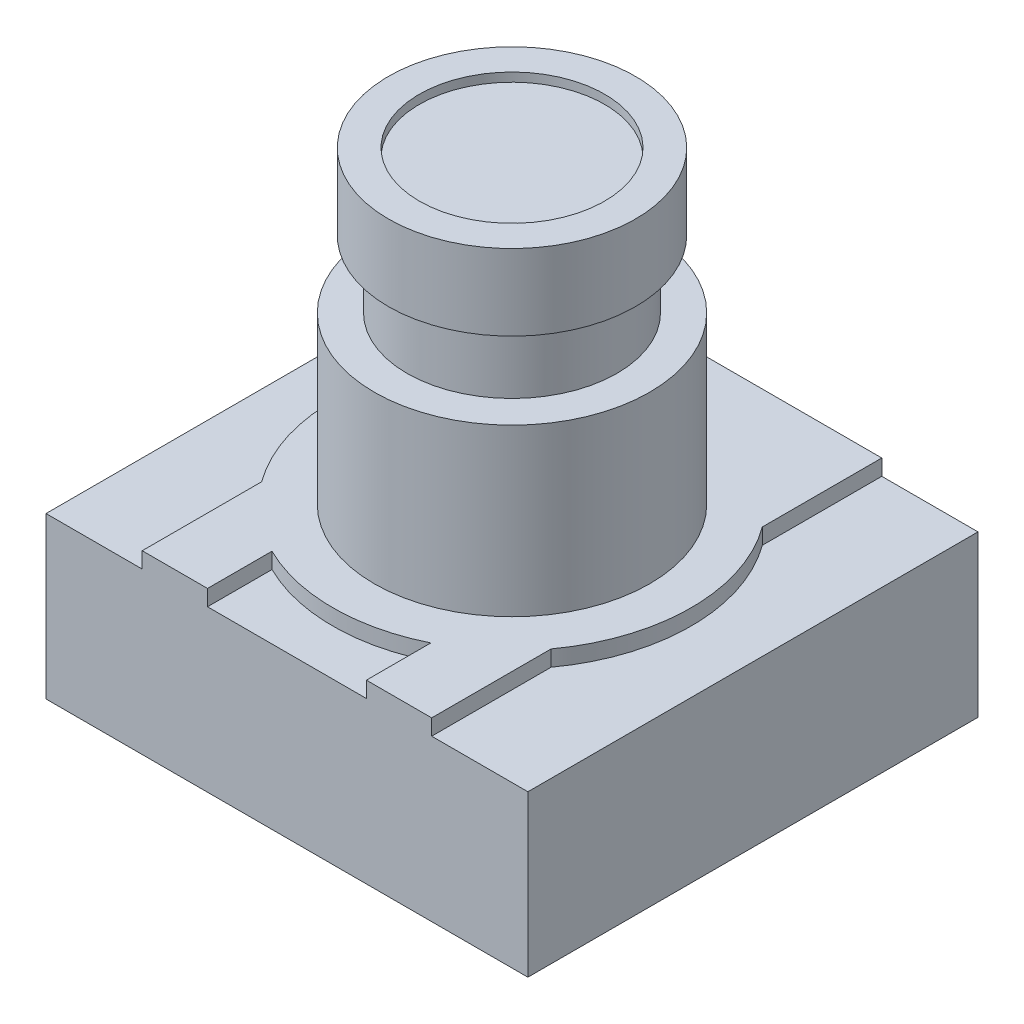
SolidWorks part; units mm, degrees
ref_plane "Front Plane" through (0, 0, 0) normal (0, 0, 1) x (1, 0, 0)
ref_plane "Top Plane" through (0, 0, 0) normal (0, 1, 0) x (1, 0, 0)
ref_plane "Right Plane" through (0, 0, 0) normal (1, 0, 0) x (0, 0, -1)
sketch "Sketch1" plane through (0, 0, 0) normal (0, 1, 0) x (1, 0, 0)
  line L1 (-13.65, 12.75) -> (13.65, 12.75)
  line L2 (-13.65, 12.75) -> (-13.65, -12.75)
  line L3 (-13.65, -12.75) -> (13.65, -12.75)
  line L4 (13.65, 12.75) -> (13.65, -12.75)
  line L5 (-13.65, 12.75) -> (13.65, -12.75) construction
  line L6 (-13.65, -12.75) -> (13.65, 12.75) construction
  point P0 (0, 0)
  dimension "D1" = 27.3
  dimension "D2" = 25.5
extrude "Boss-Extrude1" add sketch "Sketch1" along normal blind 10
sketch "Sketch2" plane through (0, 10, 0) normal (0, 1, 0) x (1, 0, 0)
  line L0 (-8.2, 12.75) -> (-8.2, -12.75)
  line L1 (13.65, 12.75) -> (-13.65, 12.75) construction
  line L2 (-13.65, -12.75) -> (13.65, -12.75) construction
  line L3 (0, 12.75) -> (0, -12.75) construction
  line L4 (8.2, 12.75) -> (8.2, -12.75)
  line L5 (-4.5, -9.0979) -> (-4.5, -12.75)
  line L6 (4.5, -9.0979) -> (4.5, -12.75)
  circle A0 centre (0, 0) radius 10.15
  line M1 (13.65, -12.75) -> (13.65, 12.75)
  line M2 (13.65, 12.75) -> (-13.65, 12.75)
  line M3 (-13.65, 12.75) -> (-13.65, -12.75)
  line M4 (-13.65, -12.75) -> (13.65, -12.75)
  dimension "D1" = 20.3
  dimension "D2" = 16.4
  dimension "D3" = 9
extrude "Cut-Extrude1" cut sketch "Sketch2" against normal blind 0.9 contours A0 L0 M2 M3 M4 | A0 L4 M4 M1 M2 | L3 A0 L5 M4 | A0 L3 L6 M4 region at (-11.175, 10, 0) region at (11.175, 10, 0) region at (-2.3825, 10, 11.262) region at (2.3825, 10, 11.262)
sketch "Sketch3" plane through (0, 10, 0) normal (0, 1, 0) x (1, 0, 0)
  circle A0 centre (0, 0) radius 7.8
  dimension "D1" = 15.6
extrude "Boss-Extrude2" add sketch "Sketch3" along normal blind 9.4
sketch "Sketch4" plane through (0, 19.4, 0) normal (0, 1, 0) x (1, 0, 0)
  circle A0 centre (0, 0) radius 5.95
  dimension "D1" = 11.9
extrude "Boss-Extrude3" add sketch "Sketch4" along normal blind 3.8
sketch "Sketch5" plane through (0, 23.2, 0) normal (0, 1, 0) x (1, 0, 0)
  circle A0 centre (0, 0) radius 7
  dimension "D1" = 14
extrude "Boss-Extrude4" add sketch "Sketch5" along normal offset from surface (4.3 mm away) 27.5 up to face at (0, 0, 0)
sketch "Sketch6" plane through (0, 27.5, 0) normal (0, 1, 0) x (1, 0, 0)
  circle A0 centre (0, 0) radius 5.25
  dimension "D1" = 10.5
extrude "Cut-Extrude2" cut sketch "Sketch6" against normal blind 0.5
sketch "Sketch7" plane through (0, 0, 0) normal (0, -1, 0) x (1, 0, 0)
  line L0 (0, 12.75) -> (0, -12.75) construction
  line L1 (-13.65, 12.75) -> (13.65, 12.75) construction
  line L2 (13.65, -12.75) -> (-13.65, -12.75) construction
  line L4 (-3.45, 11.25) -> (3.45, 11.25)
  line L5 (-3.45, 11.25) -> (-3.45, 8.05)
  line L6 (-3.45, 8.05) -> (3.45, 8.05)
  line L7 (3.45, 11.25) -> (3.45, 8.05)
  line L8 (-3.45, 11.25) -> (3.45, 8.05) construction
  line L9 (-3.45, 8.05) -> (3.45, 11.25) construction
  point P6 (0, 9.65)
  dimension "D1" = 6.9
  dimension "D2" = 3.2
  dimension "D3" = 1.5
extrude "Boss-Extrude5" add sketch "Sketch7" along normal blind 1.1
sketch "Sketch8" plane through (0, -1.1, 0) normal (0, -1, 0) x (1, 0, 0)
  line L0 (-3.45, 8.05) -> (3.45, 8.05) construction
  line L1 (-2.95, 8.05) -> (2.95, 8.05)
  line L2 (-2.95, 8.05) -> (-2.95, 10.75)
  line L3 (-2.95, 10.75) -> (2.95, 10.75)
  line L4 (2.95, 8.05) -> (2.95, 10.75)
  line L5 (0, 11.25) -> (0, 8.05) construction
  line L6 (3.45, 11.25) -> (-3.45, 11.25) construction
  line L7 (0, 10.75) -> (0, 8.05) construction
  line L8 (-3.45, 11.25) -> (-3.45, 8.05) construction
  dimension "D1" = 0.5
  dimension "D2" = 0.5
extrude "Cut-Extrude3" cut sketch "Sketch8" against normal blind 2.5
